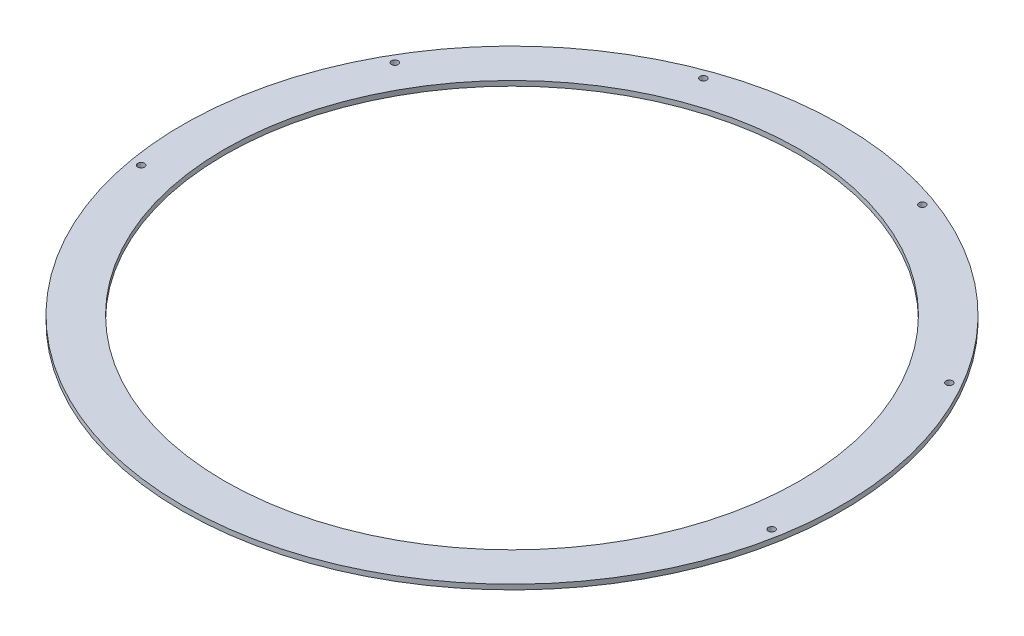
SolidWorks part; units mm, degrees
material "1.4301 (X5CrNi18-10)"
ref_plane "Vorne" through (0, 0, 0) normal (0, 0, 1) x (1, 0, 0)
ref_plane "Oben" through (0, 0, 0) normal (0, 1, 0) x (1, 0, 0)
ref_plane "Rechts" through (0, 0, 0) normal (1, 0, 0) x (0, 0, -1)
sketch "Skizze1" plane through (0, 0, 0) normal (0, 1, 0) x (1, 0, 0)
  circle A0 centre (0, 0) radius 332.5
  circle A1 centre (0, 0) radius 290
  dimension "D1" = 665
  dimension "D2" = 580
base flange "Basis-Blech1" sketch "Skizze1" thickness 5 reverse thickness direction yes parameters "D1"=0.1
hole_wizard "M8 Gewindebohrung1" positions "Skizze6" profile "Skizze7" tap size "M8" standard "Gabler-Normteile" end condition through all
sketch "Skizze6" plane through (0, 5, 0) normal (0, 1, 0) x (1, 0, 0)
  line L2 (-318.0929, -56.0884) -> (0, 0) construction
  line L4 (0, 0) -> (0, 332.5) construction
  line L7 (-110.4725, 303.5207) -> (0, 0) construction
  line L8 (0, 0) -> (-279.7262, 161.5) construction
  circle A0 centre (0, 0) radius 332.5 construction
  circle A1 centre (0, 0) radius 323 construction
  point P0 (-318.0929, -56.0884)
  point P2 (-279.7262, 161.5)
  point P4 (-110.4725, 303.5207)
  point P6 (110.4725, 303.5207)
  point P8 (279.7262, 161.5)
  point P10 (318.0929, -56.0884)
  dimension "D1" = 646
  dimension "D2" = 40
  dimension "D3" = 40
  dimension "D4" = 20
sketch "Skizze7" plane through (-318.0929, 5, 56.0884) normal (1, 0, 0) x (0, 0, 1)
  line L0 (0, 0) -> (0, 5)
  line L1 (0, 5) -> (3.4, 5)
  line L2 (3.4, 5) -> (3.4, 0)
  line L5 (3.4, 0) -> (0, 0)
  line L11 (0, -6.35) -> (0, 107.95) construction
  dimension "Bohrerdurchmesser" = 6.8
  dimension "Bohrungstiefe" = 5
cosmetic thread "Bohrungsgewinde1"
cosmetic thread "Bohrungsgewinde2"
cosmetic thread "Bohrungsgewinde3"
cosmetic thread "Bohrungsgewinde4"
cosmetic thread "Bohrungsgewinde5"
cosmetic thread "Bohrungsgewinde6"
sketch "Biegung-Linien1" [suppressed] plane through (0, 0, 0) normal (0, 1, 0) x (1, 0, 0)
sketch "Rahmen1" [suppressed] plane through (0, 0, 0) normal (0, 1, 0) x (1, 0, 0)
sheet metal parameters "Blech7" thickness 5 parameters "D1"=0.1
flat pattern "Abwicklung7" [suppressed]
sketch "Biegung-Linien2" plane through (0, 0, 0) normal (0, 1, 0) x (1, 0, 0)
sketch3d "Rahmen2" [suppressed]
  line L0 (-332.8123, -332.1872, 0) -> (332.1872, -332.8122, 0) construction
  line L1 (-332.1873, 332.8123, 0) -> (332.8122, 332.1873, 0) construction
  line L2 (-332.8123, -332.1872, 0) -> (-332.1873, 332.8123, 0) construction
  line L3 (332.1872, -332.8122, 0) -> (332.8122, 332.1873, 0) construction
sheet metal parameters "Blech8" thickness 5 parameters "D1"=0.1
flat pattern "Abwicklung7"
sketch "Biegung-Linien2" plane through (0, 0, 0) normal (0, 1, 0) x (1, 0, 0)
sketch3d "Rahmen2" [suppressed]
  line L0 (-332.8123, -332.1872, 0) -> (332.1872, -332.8122, 0) construction
  line L1 (-332.1873, 332.8123, 0) -> (332.8122, 332.1873, 0) construction
  line L2 (-332.8123, -332.1872, 0) -> (-332.1873, 332.8123, 0) construction
  line L3 (332.1872, -332.8122, 0) -> (332.8122, 332.1873, 0) construction
